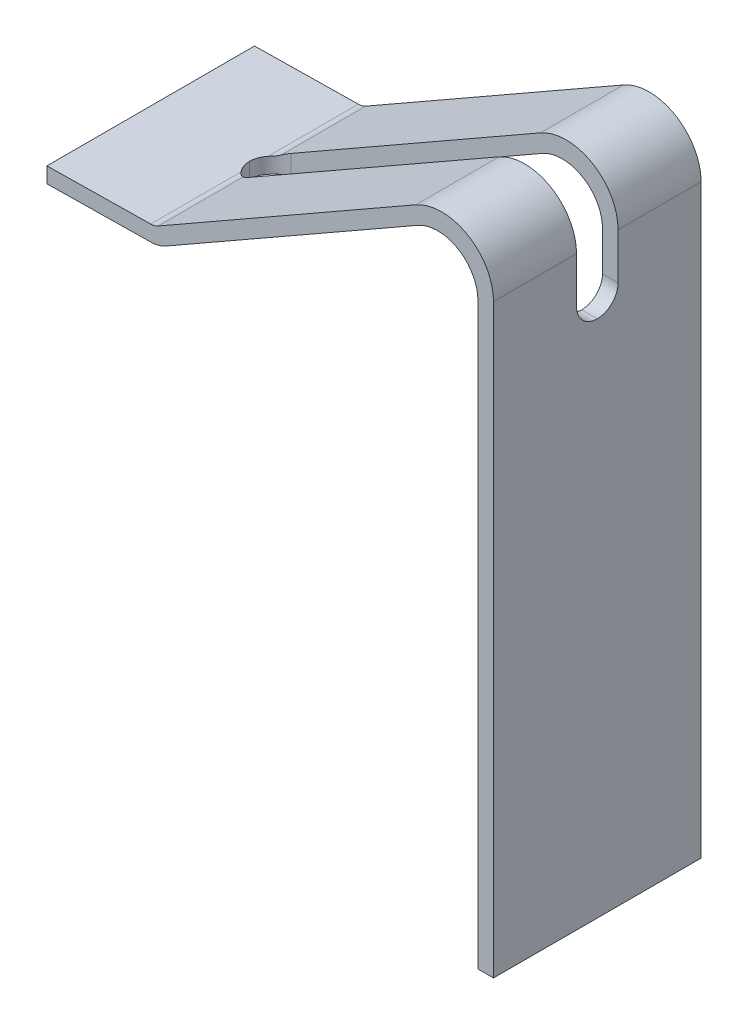
SolidWorks part; units mm, degrees
ref_plane "Спереди" through (0, 0, 0) normal (0, 0, 1) x (1, 0, 0)
ref_plane "Сверху" through (0, 0, 0) normal (0, 1, 0) x (1, 0, 0)
ref_plane "Справа" through (0, 0, 0) normal (1, 0, 0) x (0, 0, -1)
sketch "Sketch1" plane through (0, 0, 0) normal (0, 0, 1) x (1, 0, 0)
  line L0 (1.7794, -1.0759) -> (2.0794, -1.0759)
  line L1 (2.0794, -1.0759) -> (2.0794, 10.21)
  line L2 (1.7794, -1.0759) -> (1.7794, 10.0802)
  line L3 (0.6195, 10.7534) -> (-4.2318, 7.9819)
  line L4 (0.5833, 11.0783) -> (-4.3806, 8.2424)
  line L5 (-4.5206, 7.9029) -> (-6.5206, 7.8736)
  line L6 (-6.5206, 7.8736) -> (-6.525, 8.1735)
  line L7 (-6.525, 8.1735) -> (-4.525, 8.2029)
  line L8 (1.7794, 10.0802) -> (1.7794, 10.9241) construction
  line L9 (-4.3712, 7.9241) -> (-4.3712, 8.248) construction
  arc A0 (2.0794, 10.21) -> (0.5833, 11.0783) centre (1.0794, 10.21) ccw
  arc A1 (1.7794, 10.0802) -> (0.6195, 10.7534) centre (1.0041, 10.0802) ccw
  arc A2 (-4.525, 8.2029) -> (-4.3806, 8.2424) centre (-4.5294, 8.5029) ccw
  arc A3 (-4.5206, 7.9029) -> (-4.2318, 7.9819) centre (-4.5294, 8.5029) ccw
  point P19 (0, 0)
  dimension "D4" = 0.15
  dimension "D7" = 0.6
  dimension "D8" = 0.3
  dimension "D9" = 2
  dimension "D11" = 1
  dimension "D1" = 0.3
  dimension "D2" = 0.3
  dimension "D3" = 0.3
  dimension "D5" = 12
  dimension "D6" = 8.6
  dimension "D10" = 9
extrude "Boss-Extrude1" add sketch "Sketch1" along normal mid plane 4
sketch "Sketch3" plane through (0, 0, 0) normal (0, 1, 0) x (1, 0, 0)
  line L0 (2.0794, -2) -> (2.0794, 2) construction
  line L1 (2.0794, -0.4) -> (-4.6206, -0.4)
  line L2 (2.0794, -0.4) -> (2.0794, 0.4)
  line L3 (2.0794, 0.4) -> (-4.6206, 0.4)
  line L4 (-4.6206, -0.4) -> (-4.6206, 0.4)
  line L5 (2.0794, -0.4) -> (2.0794, -2) construction
  line L6 (2.0794, 0.4) -> (2.0794, 2) construction
  dimension "D1" = 0.8
  dimension "D2" = 6.7
extrude "Cut-Extrude2" cut sketch "Sketch3" against normal up to surface (3.4126 mm away) from offset 15 contours L4 L1 L2 L3 region at (-1.2706, 0, 0) up to face at (-1.8061, 9.3677, 0)
sketch "Sketch4" plane through (-4.4793, 7.8405, 0) normal (-0.4961, 0.8683, 0) x (0.8683, 0.4961, 0)
  line L0 (5.8722, 0.4) -> (6.716, 0.4) construction
  line L1 (5.8722, -0.4) -> (8.5349, -0.4)
  line L2 (5.8722, -0.4) -> (5.8722, 0.4)
  line L3 (5.8722, 0.4) -> (8.5349, 0.4)
  line L4 (8.5349, -0.4) -> (8.5349, 0.4)
extrude "Cut-Extrude3" cut sketch "Sketch4" against normal offset from surface (2.1068 mm away) 10 up to face at (1.9294, -1.0759, 0)
fillet "Fillet1" radius 0.4 4 edges at (-4.6206, 8.0515, -0.4) (-4.6206, 8.0515, 0.4) (1.9294, 8.9241, -0.4) (1.9294, 8.9241, 0.4)
equation "\"D2@Sketch1\"=\"D1@Sketch1\""
equation "\"D3@Sketch1\"=\"D1@Sketch1\""
equation "\"D4@Sketch1\"=\"D1@Sketch1\"/2"
equation "\"D7@Sketch1\"=\"D3@Sketch1\"*2"
equation "\"D8@Sketch1\"=\"D3@Sketch1\""
